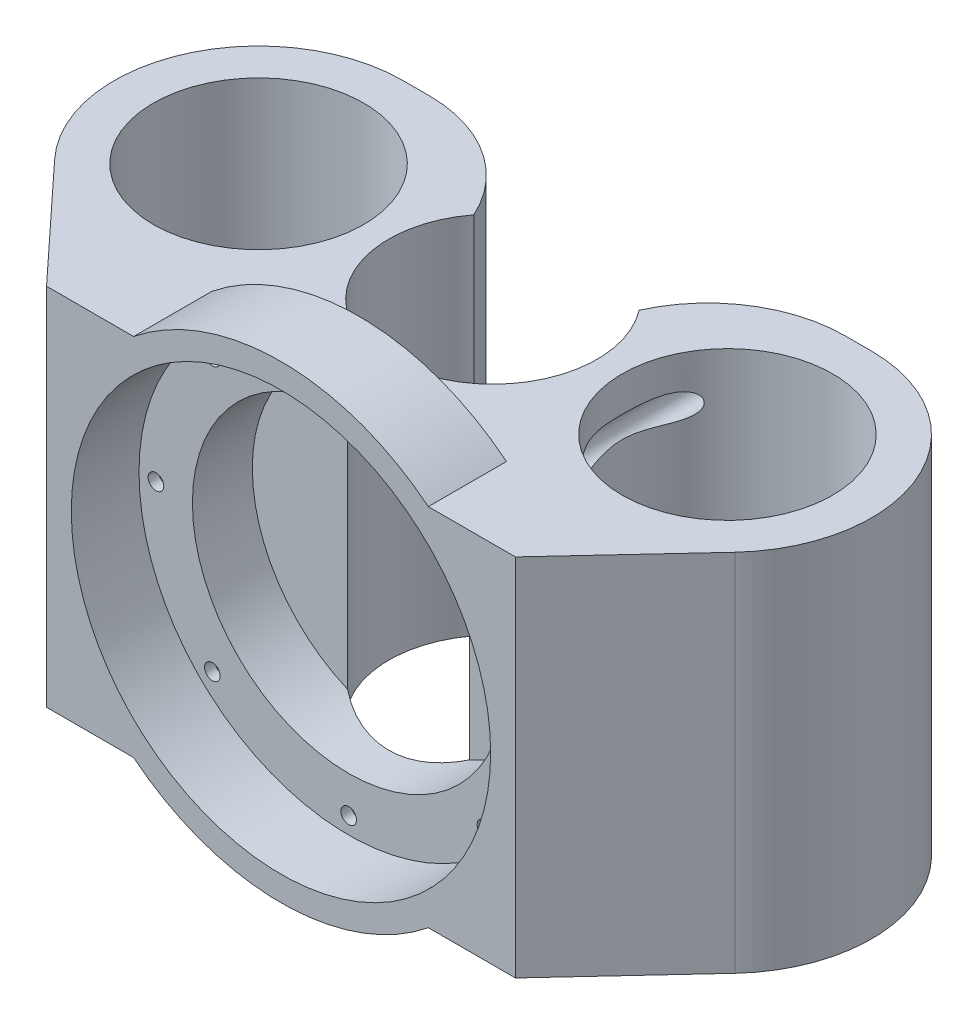
SolidWorks part; units mm, degrees
ref_plane "前视基准面" through (0, 0, 0) normal (0, 0, 1) x (1, 0, 0)
ref_plane "上视基准面" through (0, 0, 0) normal (0, 1, 0) x (1, 0, 0)
ref_plane "右视基准面" through (0, 0, 0) normal (1, 0, 0) x (0, 0, -1)
other "Configuration Table"
sketch "草图1" plane through (0, 0, 0) normal (0, 1, 0) x (1, 0, 0)
  line L0 (0, -833.3838) -> (0, 40835.8061) construction
  line L1 (-45, 27.7) -> (0, 27.7)
  line L2 (0, 27.7) -> (45, 27.7)
  line L3 (-1000, 0) -> (49000, 0) construction
  line L4 (-45, -27.7) -> (0, -27.7) construction
  line L5 (0, -27.7) -> (45, -27.7) construction
  line L6 (-65.2948, -18.8523) -> (-45, -40.7)
  line L7 (-45, -40.7) -> (45, -40.7)
  line L8 (45, -40.7) -> (65.2948, -18.8523)
  circle A0 centre (-45, 0) radius 20.2
  circle A1 centre (45, 0) radius 20.2
  circle A2 centre (0, 0) radius 20
  arc A3 (-45, 27.7) -> (-45, -27.7) centre (-45, 0) ccw construction
  arc A4 (45, 27.7) -> (45, -27.7) centre (45, 0) cw construction
  arc A5 (-45, 27.7) -> (-65.2948, -18.8523) centre (-45, 0) ccw
  arc A6 (45, 27.7) -> (65.2948, -18.8523) centre (45, 0) cw
  dimension "D1" = 40.4
  dimension "D2" = 40
  dimension "D3" = 7.5
  dimension "D4" = 90
  dimension "D5" = 13
  dimension "D6" = 90
extrude "凸台-拉伸1" add sketch "草图1" along normal blind 35 and the other way blind 35
sketch "草图9" plane through (0, 0, 40.7) normal (0, 0, 1) x (1, 0, 0)
  circle A0 centre (0, 0) radius 45
  dimension "D1" = 90
extrude "凸台-拉伸2" add sketch "草图9" against normal blind 15
sketch "草图6" plane through (0, 0, 40.7) normal (0, 0, 1) x (1, 0, 0)
  circle A0 centre (0, 0) radius 40.25
  dimension "D1" = 80.5
extrude "切除-拉伸5" cut sketch "草图6" against normal blind 13
sketch "草图7" plane through (0, 0, 27.7) normal (0, 0, 1) x (1, 0, 0)
  circle A1 centre (0, 0) radius 30
  dimension "D1" = 60
extrude "切除-拉伸6" cut sketch "草图7" against normal blind 11.5
sketch "草图8" plane through (0, -35, 0) normal (0, -1, 0) x (1, 0, 0)
  line L2 (0, -1000) -> (0, 49000) construction
  line L3 (-1000, 0) -> (49000, 0) construction
  line L4 (-15.1844, -10.5328) -> (15.1844, -10.5328) construction
  line L5 (15.1844, -10.5328) -> (39.9051, -27.7) construction
  line L6 (45, -27.7) -> (-45, -27.7) construction
  line L7 (39.9051, -27.7) -> (-39.9051, -27.7)
  line L8 (-39.9051, -27.7) -> (-15.1844, -10.5328) construction
  arc A0 (-15.1844, -10.5328) -> (15.1844, -10.5328) centre (0, -16.1933) cw
  arc A1 (-15.1844, -10.5328) -> (-39.9051, -27.7) centre (-39.9051, -1.3174) cw
  arc A2 (15.1844, -10.5328) -> (39.9051, -27.7) centre (39.9051, -1.3174) ccw
extrude "切除-拉伸7" cut sketch "草图8" against normal through all
sketch "草图11" plane through (0, 0, 25.7) normal (0, 0, -1) x (-1, 0, 0)
  line L0 (17.5, 24.367) -> (-17.5, 24.367)
  line L3 (-17.5, 24.367) -> (-20, 35)
  line L4 (28.2843, 35) -> (-28.2843, 35) construction
  line L5 (-20, 35) -> (20, 35)
  line L6 (20, 35) -> (17.5, 24.367)
  line L7 (0, -1000) -> (0, 49000) construction
  circle A0 centre (0, 0) radius 30 construction
  point P2 (0, 35)
  point P3 (0, 24.367)
  dimension "D1" = 35
  dimension "D2" = 40
sketch "草图12" plane through (0, 0, 27.7) normal (0, 0, 1) x (1, 0, 0)
  line L0 (-1000, 0) -> (49000, 0) construction
  line L1 (0, -1000) -> (0, 49000) construction
  line L2 (-707.1068, -707.1068) -> (34648.2323, 34648.2323) construction
  circle A9 centre (0, 0) radius 37 construction
  circle A14 centre (0, 37) radius 1.5
  circle A15 centre (0, -37) radius 1.5
  circle A16 centre (-37, 0) radius 1.5
  circle A17 centre (37, 0) radius 1.5
  circle A18 centre (26.163, 26.163) radius 1.5
  circle A19 centre (-26.163, 26.163) radius 1.5
  circle A20 centre (-26.163, -26.163) radius 1.5
  circle A21 centre (26.163, -26.163) radius 1.5
  point P19 (26.163, 26.163)
  dimension "D1" = 74
  dimension "D2" = 3
  dimension "D4" = 3
  dimension "D3" = 45
extrude "切除-拉伸10" cut sketch "草图12" against normal blind 10
sketch "草图13" plane through (0, 0, 25.7) normal (0, 0, 1) x (1, 0, 0)
  line L0 (-1000, 0) -> (49000, 0) construction
  line L1 (0, -1000) -> (0, 49000) construction
  line L2 (-707.1068, -707.1068) -> (34648.2323, 34648.2323) construction
  circle A0 centre (0, 37) radius 2.5
  circle A1 centre (26.163, 26.163) radius 2.5
  circle A2 centre (37, 0) radius 2.5
  circle A3 centre (26.163, -26.163) radius 2.5
  circle A4 centre (0, -37) radius 2.5
  circle A5 centre (-26.163, -26.163) radius 2.5
  circle A6 centre (-37, 0) radius 2.5
  circle A7 centre (-26.163, 26.163) radius 2.5
  dimension "D2" = 5
  dimension "D3" = 5
  dimension "D1" = 45
extrude "切除-拉伸11" cut sketch "草图13" against normal through all
